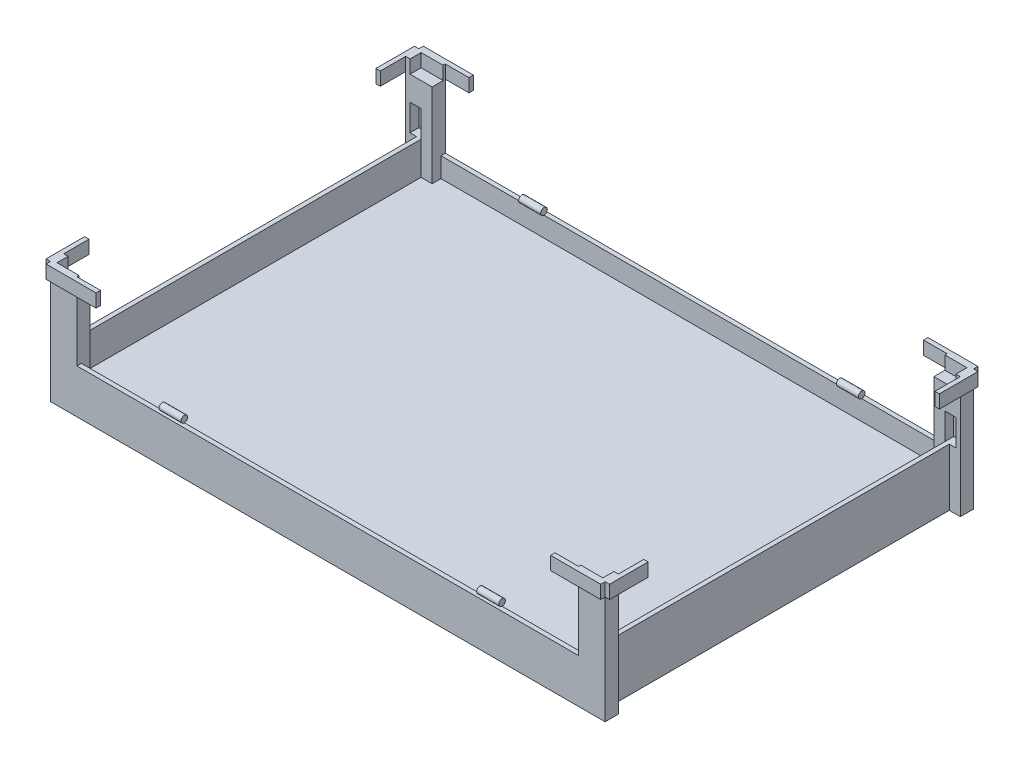
SolidWorks part; units mm, degrees
ref_plane "Piano frontale" through (0, 0, 0) normal (0, 0, 1) x (1, 0, 0)
ref_plane "Piano superiore" through (0, 0, 0) normal (0, 1, 0) x (1, 0, 0)
ref_plane "Piano destro" through (0, 0, 0) normal (1, 0, 0) x (0, 0, -1)
sketch "Schizzo1" plane through (0, 0, 0) normal (0, 1, 0) x (1, 0, 0)
  line L1 (-603.5, -417.5) -> (603.5, -417.5)
  line L2 (-603.5, -417.5) -> (-603.5, 417.5)
  line L3 (-603.5, 417.5) -> (603.5, 417.5)
  line L4 (603.5, -417.5) -> (603.5, 417.5)
  line L5 (-603.5, -417.5) -> (603.5, 417.5) construction
  line L6 (-603.5, 417.5) -> (603.5, -417.5) construction
  point P0 (0, 0)
  dimension "D1" = 1207
  dimension "D2" = 835
extrude "Estrusione-Estrusione2" add sketch "Schizzo1" along normal blind 100 contours L3 L4 L1 L2
shell "Svuota1" thickness 10 removed face at (0, 0, 0) removed face at (0, 100, 0)
sketch "Schizzo6" plane through (0, 0, 417.5) normal (0, 0, 1) x (1, 0, 0)
  line L0 (-603.5, 100) -> (-603.5, 0) construction
  line L1 (-603.5, 55) -> (603.5, 55)
  line L2 (-603.5, 55) -> (-603.5, 45)
  line L3 (-603.5, 45) -> (603.5, 45)
  line L4 (603.5, 55) -> (603.5, 45)
  line L5 (603.5, 100) -> (603.5, 0) construction
  point P8 (603.5, 50)
  point P9 (603.5, 50)
  dimension "D1" = 10
extrude "Estrusione-Estrusione3" add sketch "Schizzo6" against normal up to next
sketch "Schizzo12" plane through (0, 100, 0) normal (0, 1, 0) x (1, 0, 0)
  line L0 (-603.5, -417.5) -> (603.5, -417.5) construction
  line L1 (603.5, 417.5) -> (593.5, 417.5)
  line L2 (603.5, 417.5) -> (603.5, -417.5)
  line L3 (603.5, -417.5) -> (593.5, -417.5)
  line L4 (593.5, 417.5) -> (593.5, -417.5)
  line L5 (593.5, -407.5) -> (593.5, 407.5) construction
  line L6 (-593.5, -407.5) -> (-593.5, 407.5) construction
  line L7 (-603.5, 417.5) -> (-593.5, 417.5)
  line L8 (-603.5, 417.5) -> (-603.5, -417.5)
  line L9 (-603.5, -417.5) -> (-593.5, -417.5)
  line L10 (-593.5, 417.5) -> (-593.5, -417.5)
extrude "Estrusione-Estrusione10" add sketch "Schizzo12" along normal blind 30
sketch "Schizzo7" plane through (0, 0, 417.5) normal (0, 0, 1) x (1, 0, 0)
  line L0 (628.5, 0) -> (568.5, 0)
  line L1 (-603.5, 0) -> (603.5, 0) construction
  line L2 (568.5, 0) -> (568.5, 275)
  line L3 (568.5, 275) -> (628.5, 275)
  line L4 (628.5, 275) -> (628.5, 0)
  line L5 (603.5, 130) -> (603.5, 0) construction
  dimension "D1" = 60
  dimension "D2" = 275
  dimension "D3" = 25
extrude "Estrusione-Estrusione4" add sketch "Schizzo7" against normal blind 10
sketch "Schizzo8" plane through (628.5, 0, 0) normal (1, 0, 0) x (0, 0, -1)
  line L0 (-407.5, 0) -> (-387.5, 0)
  line L1 (-407.5, 130) -> (-387.5, 130)
  line L2 (-387.5, 0) -> (-387.5, 275)
  line L3 (-387.5, 275) -> (-407.5, 275)
  line L4 (-407.5, 275) -> (-407.5, 0)
  line L6 (-407.5, 0) -> (417.5, 0) construction
  line L7 (-407.5, 0) -> (-407.5, 275) construction
  line L8 (-407.5, 130) -> (417.5, 130) construction
  line M3 (-407.5, 0) -> (-407.5, 275)
  dimension "D1" = 20
extrude "Estrusione-Estrusione5" add sketch "Schizzo8" against normal blind 10 contours L2 L3 L1 M3 region at (628.5, 202.5, 397.5)
sketch "Schizzo9" plane through (0, 130, 0) normal (0, 1, 0) x (1, 0, 0)
  line L0 (588.5, -417.5) -> (588.5, -387.5)
  line L1 (588.5, -387.5) -> (593.5, -387.5)
  line L3 (618.5, -387.5) -> (628.5, -387.5) construction
  line L4 (588.5, -417.5) -> (593.5, -417.5)
  line L5 (593.5, -417.5) -> (593.5, -387.5)
  line L6 (593.5, 417.5) -> (593.5, 407.5) construction
  dimension "D1" = 5
extrude "Estrusione-Estrusione6" add sketch "Schizzo9" against normal up to next
sketch "Schizzo10" plane through (0, 130, 0) normal (0, 1, 0) x (1, 0, 0)
  line L0 (588.5, -417.5) -> (588.5, -387.5)
  line L2 (588.5, -387.5) -> (593.5, -387.5)
  line L3 (593.5, -387.5) -> (593.5, -417.5)
  line L4 (593.5, -417.5) -> (588.5, -417.5)
extrude "Estrusione-Estrusione7" add sketch "Schizzo10" along normal blind 65
sketch "Schizzo11" plane through (593.5, -365, 0) normal (-1, 0, 0) x (0, 1, 0)
  line L0 (560, -387.5) -> (555, -387.5)
  line L2 (555, -387.5) -> (555, -407.5)
  line L4 (555, -407.5) -> (560, -407.5)
  line L5 (560, -407.5) -> (560, -387.5)
  dimension "D1" = 5
extrude "Estrusione-Estrusione8" add sketch "Schizzo11" against normal up to next
extrude "Estrusione-Estrusione9" add sketch "Schizzo8<3>" against normal up to next contours L0 L2 L1 M3 region at (628.5, 65, 397.5)
sketch "Schizzo8<3>" plane through (628.5, 0, 0) normal (1, 0, 0) x (0, 0, -1) same geometry as "Schizzo8"
sketch "Schizzo14" plane through (628.5, 0, 0) normal (1, 0, 0) x (0, 0, -1)
  line L0 (-387.5, 0) -> (-387.5, 275) construction
  line L1 (-417.5, 275) -> (-330, 275)
  line L2 (-417.5, 275) -> (-417.5, 245)
  line L3 (-417.5, 245) -> (-330, 245)
  line L4 (-330, 275) -> (-330, 245)
  dimension "D1" = 57.5
  dimension "D2" = 30
extrude "Estrusione-Estrusione12" add sketch "Schizzo14" along normal blind 10
sketch "Schizzo15" plane through (0, 275, 0) normal (0, 1, 0) x (1, 0, 0)
  line L0 (618.5, -387.5) -> (618.5, -407.5) construction
  line L1 (568.5, -407.5) -> (618.5, -407.5)
  line L2 (568.5, -407.5) -> (568.5, -412.5)
  line L3 (568.5, -412.5) -> (618.5, -412.5)
  line L4 (618.5, -407.5) -> (618.5, -412.5)
  dimension "D1" = 5
extrude "Taglio-Estrusione1" cut sketch "Schizzo15" against normal up to surface (30 mm away) up to face at (632.5, 245, 376.5)
sketch "Schizzo16" plane through (0, 55, 0) normal (0, 1, 0) x (1, 0, 0)
  line L1 (568.5, -407.5) -> (588.5, -407.5)
  line L2 (568.5, -407.5) -> (568.5, -387.5)
  line L3 (568.5, -387.5) -> (588.5, -387.5)
  line L4 (588.5, -407.5) -> (588.5, -387.5)
extrude "Estrusione-Estrusione13" add sketch "Schizzo16" along normal up to surface (190 mm away) up to face at (593.5, 245, 410)
sketch "Schizzo17" plane through (0, 195, 0) normal (0, 1, 0) x (1, 0, 0)
  line L4 (588.5, -407.5) -> (618.5, -407.5)
  line L5 (618.5, -407.5) -> (618.5, -387.5)
  line L6 (618.5, -387.5) -> (588.5, -387.5)
  line L7 (588.5, -387.5) -> (588.5, -407.5)
  line L8 (588.5, -407.5) -> (618.5, -407.5)
  line L9 (618.5, -407.5) -> (618.5, -387.5)
  line L10 (618.5, -387.5) -> (588.5, -387.5)
  line L11 (588.5, -387.5) -> (588.5, -407.5)
  dimension "D1" = 0
extrude "Estrusione-Estrusione14" add sketch "Schizzo17" along normal up to surface (50 mm away) up to face at (591.8333, 245, 402.5)
sketch "Schizzo18" plane through (0, 0, 417.5) normal (0, 0, 1) x (1, 0, 0)
  line L0 (568.5, 275) -> (568.5, 100) construction
  line L1 (628.5, 245) -> (515, 245)
  line L2 (628.5, 245) -> (628.5, 275)
  line L3 (628.5, 275) -> (515, 275)
  line L4 (515, 245) -> (515, 275)
  line L5 (638.5, 275) -> (568.5, 275) construction
  dimension "D1" = 53.5
extrude "Estrusione-Estrusione15" add sketch "Schizzo18" along normal blind 10
mirror "Specchia1" about plane through (0, 0, 0) normal (0, 0, 1) of "Estrusione-Estrusione15", "Estrusione-Estrusione12", "Estrusione-Estrusione4", "Estrusione-Estrusione5", "Estrusione-Estrusione6", "Estrusione-Estrusione7", "Estrusione-Estrusione8", "Estrusione-Estrusione9", "Taglio-Estrusione1", "Estrusione-Estrusione13", "Estrusione-Estrusione14"
mirror "Specchia2" about plane through (0, 0, 0) normal (1, 0, 0) of "Estrusione-Estrusione4", "Estrusione-Estrusione5", "Estrusione-Estrusione6", "Estrusione-Estrusione7", "Estrusione-Estrusione8", "Specchia1"
sketch "Schizzo13" plane through (568.5, 0, 0) normal (-1, 0, 0) x (0, 0, 1)
  line L0 (-417.5, 100) -> (-407.5, 100) construction
  line L1 (-407.5, 55) -> (-407.5, 100) construction
  circle A0 centre (-407.5, 107.5) radius 7.5
  dimension "D1" = 15
extrude "Estrusione-Estrusione11" add sketch "Schizzo13" against normal blind 50 from offset 233.5 separate body
mirror "Specchia3" about plane through (0, 0, 0) normal (1, 0, 0) of bodies 120
mirror "Specchia4" about plane through (0, 0, 0) normal (0, 0, 1) of bodies 121 120
